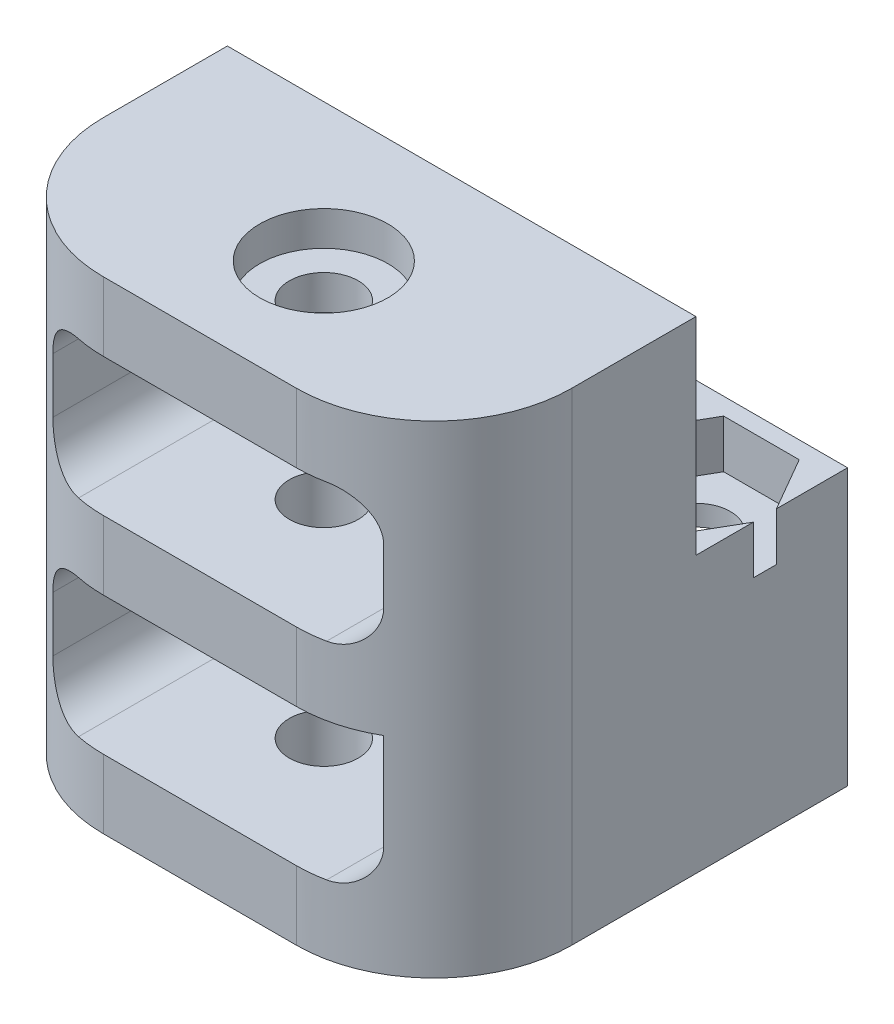
SolidWorks part; units mm, degrees
ref_plane "Alzado" through (0, 0, 0) normal (0, 0, 1) x (1, 0, 0)
ref_plane "Planta" through (0, 0, 0) normal (0, 1, 0) x (1, 0, 0)
ref_plane "Vista lateral" through (0, 0, 0) normal (1, 0, 0) x (0, 0, -1)
sketch "Croquis21" plane through (0, 0, 0) normal (0, 1, 0) x (1, 0, 0)
  line L5 (17.279, 0) -> (51.279, 0)
  line L6 (17.279, 0) -> (17.279, -30)
  line L7 (17.279, -30) -> (51.279, -30)
  line L8 (51.279, 0) -> (51.279, -30)
  dimension "D1" = 34
  dimension "D2" = 30
extrude "Saliente-Extruir4" add sketch "Croquis21" along normal mid plane 35 separate body
sketch "Croquis22" plane through (0, 0, 30) normal (0, 0, 1) x (1, 0, 0)
  line L1 (17.279, 17.5) -> (51.279, 17.5) construction
  line L2 (22.279, 12.5) -> (46.279, 12.5)
  line L3 (22.279, 12.5) -> (22.279, 2.5)
  line L4 (22.279, 2.5) -> (46.279, 2.5)
  line L5 (46.279, 12.5) -> (46.279, 2.5)
  line L6 (51.279, 17.5) -> (51.279, -17.5) construction
  line L9 (34.279, 2.5) -> (34.279, -2.5) construction
  line L10 (22.279, 12.5) -> (46.279, 12.5)
  line L11 (22.279, 12.5) -> (22.279, 2.5)
  line L12 (22.279, 2.5) -> (46.279, 2.5)
  line L13 (46.279, 12.5) -> (46.279, 2.5)
  line L14 (34.279, 0) -> (40.6945, 0) construction
  line L15 (22.279, -2.5) -> (46.279, -2.5)
  line L16 (46.279, -12.5) -> (46.279, -2.5)
  line L17 (22.279, -12.5) -> (46.279, -12.5)
  line L18 (22.279, -12.5) -> (22.279, -2.5)
  line L19 (34.279, -12.5) -> (34.279, -17.5) construction
  line L20 (17.279, -17.5) -> (51.279, -17.5) construction
  dimension "D1" = 10
  dimension "D2" = 24
  dimension "D3" = 5
  dimension "D4" = 5
  dimension "D5" = 5
extrude "Cortar-Extruir17" cut sketch "Croquis22" against normal up to next contours L5 L2 L3 L4 | L18 L17 L16 L15 region at (34.279, 7.5, 30) region at (34.279, -7.5, 30)
sketch "Croquis23" plane through (17.279, 0, 0) normal (-1, 0, 0) x (0, 0, 1)
  line L0 (0, 2.5) -> (11, 2.5)
  line L1 (0, 17.5) -> (30, 17.5) construction
  line L2 (0, 17.5) -> (11, 17.5)
  line L3 (0, 17.5) -> (0, 2.5)
  line L5 (11, 17.5) -> (11, 2.5)
  dimension "D1" = 11
  dimension "D2" = 15
extrude "Cortar-Extruir18" cut sketch "Croquis23" against normal up to next
sketch "Croquis24" plane through (0, 17.5, 0) normal (0, 1, 0) x (1, 0, 0)
  line L0 (17.279, -6) -> (22.279, -6) construction
  line L1 (17.279, 0) -> (17.279, -11) construction
  line L2 (22.279, -6) -> (22.279, 0) construction
  line L3 (51.279, 0) -> (17.279, 0) construction
  line L6 (34.279, -21) -> (34.279, -30) construction
  line L7 (17.279, -30) -> (51.279, -30) construction
  line L11 (34.279, 0) -> (34.279, -3.4347) construction
  circle A0 centre (22.279, -6) radius 2.5
  circle A1 centre (34.279, -21) radius 2.5
  circle A2 centre (46.279, -6) radius 2.5
  point P21 (34.279, -30)
  dimension "D4" = 5
  dimension "D5" = 5
  dimension "D1" = 5
  dimension "D2" = 6
  dimension "D3" = 9
extrude "Cortar-Extruir19" cut sketch "Croquis24" against normal up to surface (35 mm away) up to face at (34.279, -17.5, 15)
sketch "Croquis25" plane through (0, 17.5, 0) normal (0, 1, 0) x (1, 0, 0)
  circle A0 centre (34.279, -21) radius 4.65
  dimension "D1" = 9.3
extrude "Cortar-Extruir20" cut sketch "Croquis25" against normal blind 2.5
sketch "Croquis26" plane through (0, 2.5, 0) normal (0, 1, 0) x (1, 0, 0)
  line L7 (27.7638, -6) -> (25.0214, -1.25)
  line L8 (25.0214, -1.25) -> (19.5366, -1.25)
  line L9 (19.5366, -1.25) -> (16.7942, -6)
  line L10 (16.7942, -6) -> (19.5366, -10.75)
  line L11 (19.5366, -10.75) -> (25.0214, -10.75)
  line L12 (25.0214, -10.75) -> (27.7638, -6)
  line L13 (51.7638, -6) -> (49.0214, -1.25)
  line L14 (49.0214, -1.25) -> (43.5366, -1.25)
  line L15 (43.5366, -1.25) -> (40.7942, -6)
  line L16 (40.7942, -6) -> (43.5366, -10.75)
  line L17 (43.5366, -10.75) -> (49.0214, -10.75)
  line L18 (49.0214, -10.75) -> (51.7638, -6)
  circle A0 centre (22.279, -6) radius 4.75 construction
  circle A1 centre (46.279, -6) radius 4.75 construction
  dimension "D1" = 9.5
  dimension "D2" = 9.5
extrude "Cortar-Extruir21" cut sketch "Croquis26" against normal blind 3.5
fillet "Redondeo2" radius 10 2 edges at (51.279, 0, 30) (17.279, 0, 30)
fillet "Redondeo3" radius 3 7 edges at (46.279, 12.5, 19.8301) (46.279, 2.5, 19.8301) (46.279, -12.5, 18.5801) (22.279, -12.5, 18.5801) (22.279, -2.5, 18.5801) (22.279, 12.5, 19.8301) (22.279, 2.5, 19.8301)
